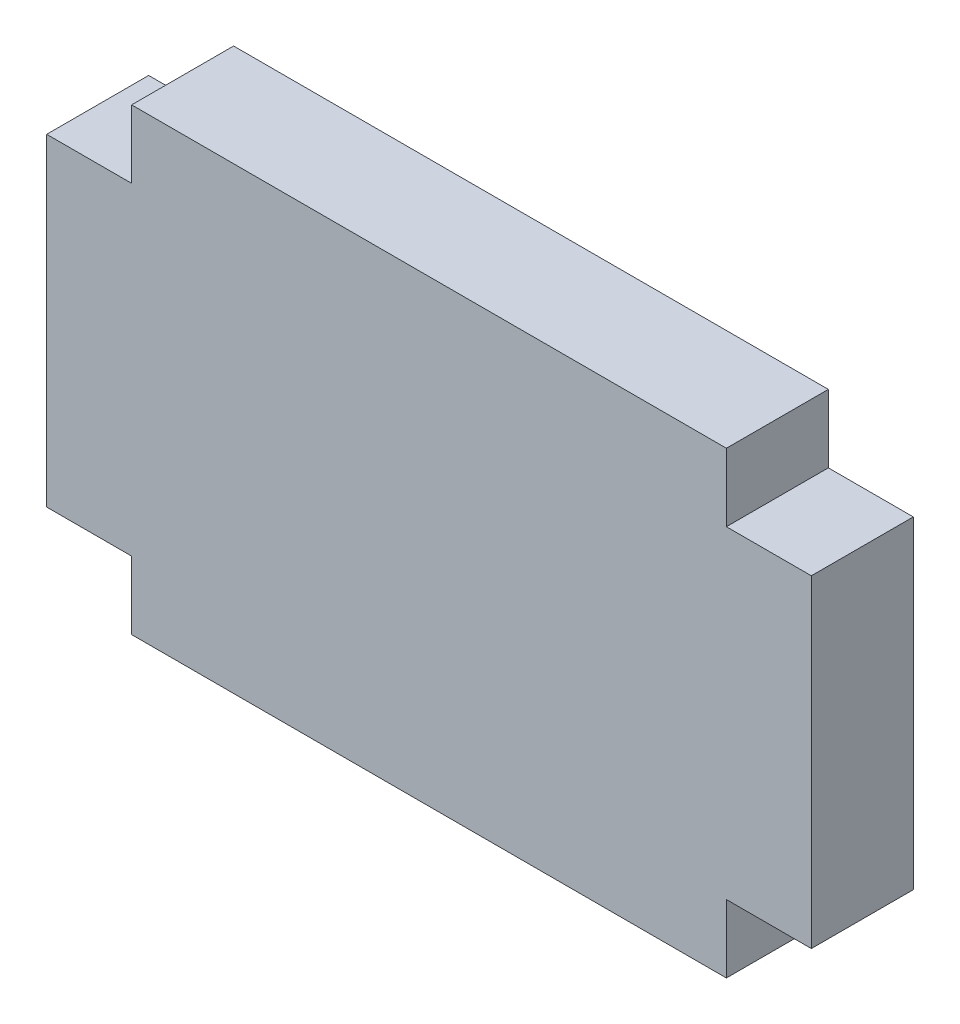
SolidWorks part; units mm, degrees
material "Acrílico (médio-alto impacto)"
ref_plane "Plano frontal" through (0, 0, 0) normal (0, 0, 1) x (1, 0, 0)
ref_plane "Plano superior" through (0, 0, 0) normal (0, 1, 0) x (1, 0, 0)
ref_plane "Plano direito" through (0, 0, 0) normal (1, 0, 0) x (0, 0, -1)
sketch "Esboço1" plane through (0, 0, 0) normal (0, 0, 1) x (1, 0, 0)
  line L0 (0, 0) -> (22.5, 0) construction
  line L1 (-22.5, -9.5) -> (22.5, -9.5)
  line L2 (-22.5, -9.5) -> (-22.5, 9.5)
  line L3 (-22.5, 9.5) -> (22.5, 9.5)
  line L4 (22.5, -9.5) -> (22.5, 9.5)
  line L5 (-22.5, -9.5) -> (22.5, 9.5) construction
  line L6 (-22.5, 9.5) -> (22.5, -9.5) construction
  line L7 (17.5, 13.5) -> (-17.5, 13.5)
  line L8 (17.5, 13.5) -> (17.5, 9.5)
  line L9 (17.5, 9.5) -> (-17.5, 9.5)
  line L10 (-17.5, 13.5) -> (-17.5, 9.5)
  line L11 (17.5, 13.5) -> (-17.5, 9.5) construction
  line L12 (17.5, 9.5) -> (-17.5, 13.5) construction
  line L13 (17.5, -9.5) -> (-17.5, -9.5)
  line L14 (-17.5, -13.5) -> (-17.5, -9.5)
  line L15 (17.5, -13.5) -> (-17.5, -13.5)
  line L16 (17.5, -13.5) -> (17.5, -9.5)
  point P0 (0, 0)
  point P6 (0, 11.5)
  dimension "D1" = 4
  dimension "D2" = 35
  dimension "D3" = 19
  dimension "D4" = 45
extrude "Ressalto-extrusão1" add sketch "Esboço1" along normal blind 6 contours L1 L4 L3 L2 | L7 L10 L3 L8 | L15 L16 L1 L14 region at (0, 0, 0) region at (0, -11.5, 0) region at (0, 11.5, 0)
